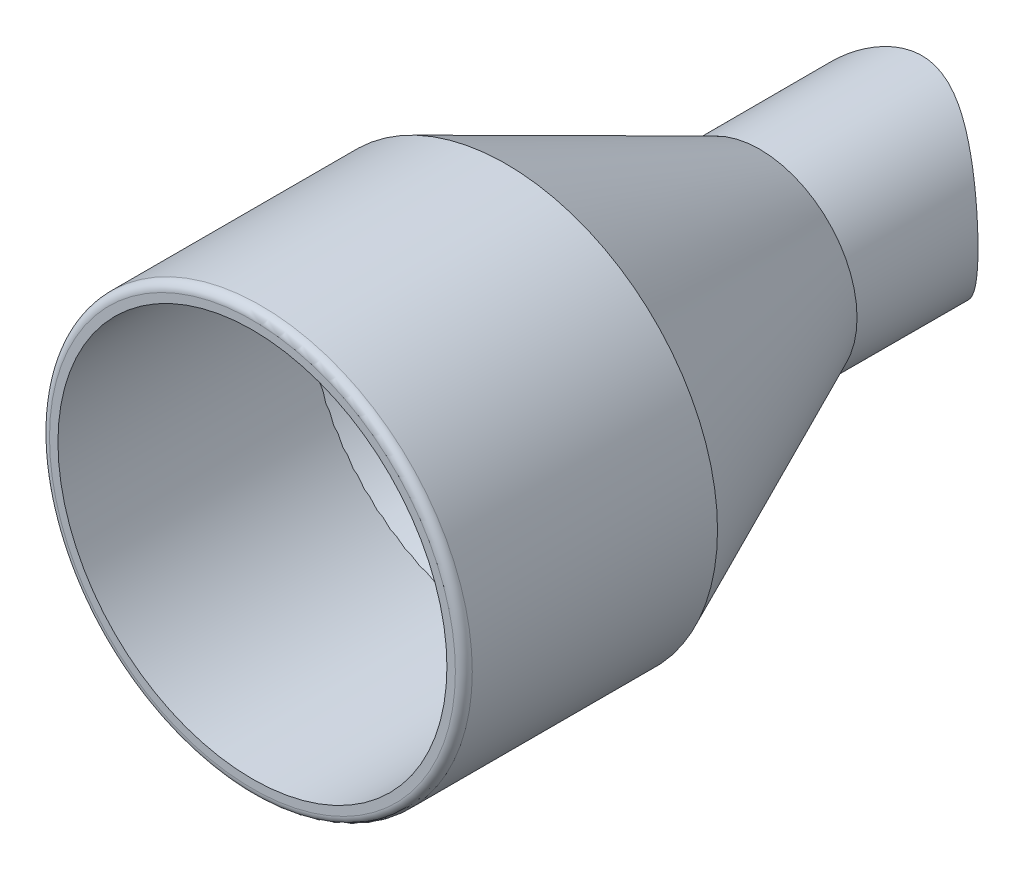
SolidWorks part; units mm, degrees
ref_plane "Front Plane" through (0, 0, 0) normal (0, 0, 1) x (1, 0, 0)
ref_plane "Top Plane" through (0, 0, 0) normal (0, 1, 0) x (1, 0, 0)
ref_plane "Right Plane" through (0, 0, 0) normal (1, 0, 0) x (0, 0, -1)
sketch "Sketch1" plane through (0, 0, 0) normal (0, 0, 1) x (1, 0, 0)
  circle A0 centre (0, 0) radius 25
  circle A1 centre (0, 0) radius 23
  dimension "D1" = 50
  dimension "D2" = 2
extrude "Boss-Extrude1" add sketch "Sketch1" along normal blind 30
sketch "Sketch2" plane through (0, 0, 0) normal (0, 0, -1) x (-1, 0, 0)
  circle A0 centre (0, 0) radius 25 construction
  point P0 (0, 0)
  point P1 (0, 25)
sketch "Sketch4" plane through (0, 0, 30) normal (0, 0, 1) x (1, 0, 0)
  point P0 (0, 25)
ref_plane "Plane1" through (0, 0, 0) normal (1, 0, 0) x (0, 0, -1)
sketch "Sketch5" plane through (0, 0, 0) normal (1, 0, 0) x (0, 0, -1)
  line L0 (0, 0) -> (30, 0)
  line L3 (30, 11.5) -> (0, 25)
  line L4 (0, -25) -> (0, 25) construction
  dimension "D1" = 30
  dimension "D2" = 30
  dimension "D3" = 11.5
revolve "Revolve-Thin1" add sketch "Sketch5" angle 360 about L0 wall 2
sketch3d "3DSketch1"
  circle A0 centre (0, 0, -29.1793) radius 9.6762 construction
  point P0 (7.2554, -6.4021, -29.1793)
  point P3 (0, 0, -19.5031)
sketch3d "3DSketch2"
  circle A0 centre (0, 0, -29.1793) radius 9.6762 construction
  point P0 (-9.6587, -0.5803, -29.1793)
  point P3 (0, 0, -19.5031)
ref_plane "Plane4" through (0, 0, -29.1793) normal (0, 0, -1) x (-1, 0, 0)
sketch "Sketch6" plane through (0, 0, -29.1793) normal (0, 0, -1) x (-1, 0, 0)
  circle A0 centre (0, 0) radius 9.6762
  circle A1 centre (0, 0) radius 12.5
  circle A2 centre (0, 0) radius 9.6762 construction
fillet "Fillet1" radius 1 1 edges at (25, 0, 30)
sketch "Sketch7" plane through (0, 0, -29.1793) normal (0, 0, -1) x (-1, 0, 0)
  circle A0 centre (0, 0) radius 9.6762
  circle A1 centre (0, 0) radius 11.5
  circle A2 centre (0, 0) radius 11.5 construction
  circle A3 centre (0, 0) radius 9.6762 construction
extrude "Boss-Extrude2" add sketch "Sketch7" along normal blind 20
sketch "Sketch8" plane through (0, 0, 0) normal (1, 0, 0) x (0, 0, -1)
  circle A0 centre (60.3036, 0) radius 16
  dimension "D1" = 32
extrude "Cut-Extrude1" cut sketch "Sketch8" against normal mid plane 30
